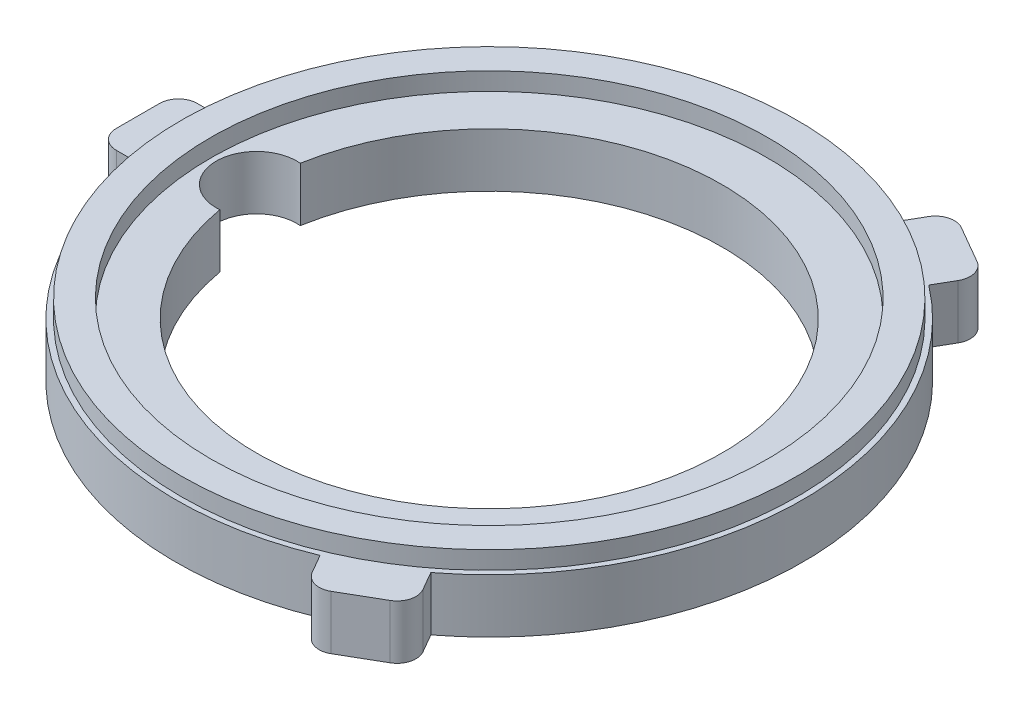
SolidWorks part; units mm, degrees
ref_plane "Ebene vorne" through (0, 0, 0) normal (0, 0, 1) x (1, 0, 0)
ref_plane "Ebene oben" through (0, 0, 0) normal (0, 1, 0) x (1, 0, 0)
ref_plane "Ebene rechts" through (0, 0, 0) normal (1, 0, 0) x (0, 0, -1)
sketch "Skizze1" plane through (0, 0, 0) normal (0, 1, 0) x (1, 0, 0)
  line L1 (-6.5, 0.75) -> (-5.2381, 0.75)
  line L2 (-6.5, 0.75) -> (-6.5, -0.75)
  line L3 (-6.5, -0.75) -> (-5.2381, -0.75)
  line L4 (-5.2381, 0.75) -> (-5.2381, -0.75)
  circle A0 centre (0, 0) radius 5.8
  circle A1 centre (0, 0) radius 4.3
extrude "Aufsatz-Linear austragen1" add sketch "Skizze1" along normal blind 1 contours A0
extrude "Aufsatz-Linear austragen2" add sketch "Skizze1<3>" along normal blind 1 contours L3 L4 L1 L2
sketch "Skizze1<3>" plane through (0, 0, 0) normal (0, 1, 0) x (1, 0, 0) same geometry as "Skizze1"
sketch "Skizze4" plane through (0, 1, 0) normal (0, 1, 0) x (1, 0, 0)
  circle A0 centre (0, 0) radius 4.305
extrude "Schnitt-Linear austragen1" cut sketch "Skizze4" against normal blind 1 contours A0
sketch "Skizze5" plane through (0, 1, 0) normal (0, 1, 0) x (1, 0, 0)
  circle A0 centre (0, 0) radius 4.305 construction
  circle A1 centre (-4.305, 0) radius 0.7477
extrude "Schnitt-Linear austragen2" cut sketch "Skizze5" against normal blind 1
pattern_circular "Kreismuster1" count 3 over 360 about axis through (0, 0, 0) along (0, 1, 0) of "Aufsatz-Linear austragen2"
fillet "Verrundung2" radius 0.35 6 edges at (2.6005, 0.5, 6.0042) (3.8995, 0.5, 5.2542) (3.8995, 0.5, -5.2542) (2.6005, 0.5, -6.0042) (-6.5, 0.5, 0.75) (-6.5, 0.5, -0.75)
sketch "Skizze6" plane through (0, 1, 0) normal (0, 1, 0) x (1, 0, 0)
  circle A0 centre (0, 0) radius 5.1526
  circle A1 centre (0, 0) radius 5.7
extrude "Aufsatz-Linear austragen3" add sketch "Skizze6" along normal blind 0.33
